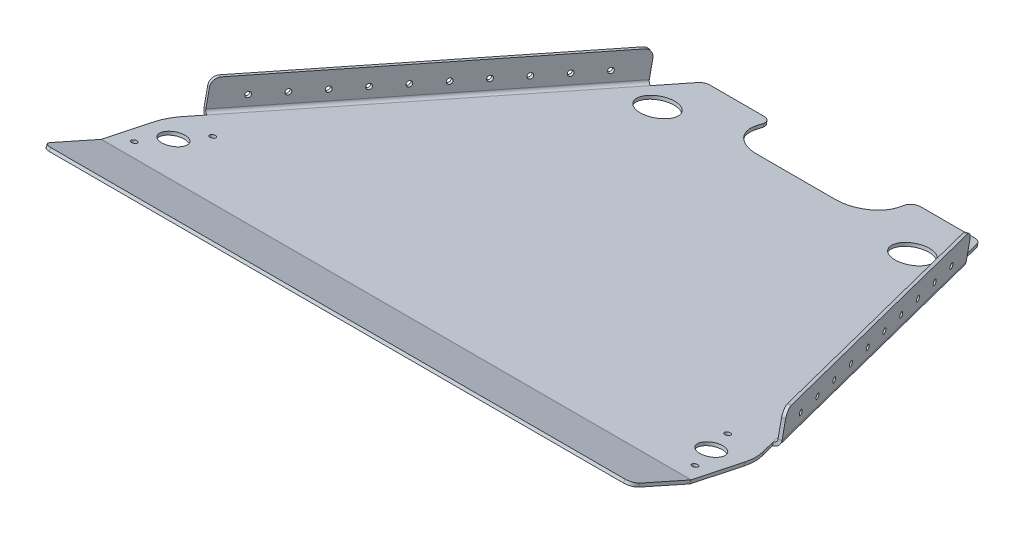
SolidWorks part; units mm, degrees
note: The reader was unsure of these and kept them because the rebuilt part matched: flange length of "Edge-Flange1", "Edge-Flange3".
material "PC High Viscosity"
ref_plane "Front Plane" through (0, 0, 0) normal (0, 0, 1) x (1, 0, 0)
ref_plane "Top Plane" through (0, 0, 0) normal (0, 1, 0) x (1, 0, 0)
ref_plane "Right Plane" through (0, 0, 0) normal (1, 0, 0) x (0, 0, -1)
sketch "Sketch3" plane through (0, 0, 0) normal (1, 0, 0) x (0, 0, -1)
  line L2 (0, 0) -> (233.2096, 0) construction
  line L7 (0, 25.4) -> (233.2096, 25.4) construction
  line L8 (0, 25.4) -> (233.2096, 25.4) construction
  line L9 (18.9735, 25.4) -> (-49981.0265, 25.4) construction
  line L10 (-119.4976, 25.4) -> (-118.9695, 27.8845)
  line L11 (-119.4976, 25.4) -> (-477.9904, 101.6)
  line L12 (-477.7235, 104.14) -> (-118.9695, 27.8845)
  line L16 (-477.7235, 104.14) -> (-477.9904, 101.6)
  circle A0 centre (4.6096, 88.9) radius 88.9 construction
  dimension "D3" = 177.8
  dimension "D4" = 228.6
  dimension "D8" = 25.4
ref_plane "Plane1" through (0, 0, 0) normal (0, 0.9781, -0.2079) x (0, 0.2079, 0.9781)
sketch "Sketch19" plane through (0, 0, 0) normal (0, 0.9781, -0.2079) x (1, 0, 0)
  line L0 (238.125, -441.336) -> (111.125, -127)
  line L1 (-111.125, -127) -> (-57.15, -127)
  line L3 (-238.125, -495.3) -> (238.125, -495.3)
  line L5 (-111.125, -127) -> (-238.125, -441.336)
  line L7 (-238.125, -495.3) -> (-238.125, -441.336)
  line L8 (-238.125, -440.7496) -> (-238.125, -428.0575) construction
  line L9 (238.125, -441.336) -> (238.125, -495.3)
  line L10 (-238.125, -441.336) -> (-259.9279, -495.3) construction
  line L11 (-57.15, -139.7) -> (-57.15, -127)
  line L12 (-31.75, -165.1) -> (31.75, -165.1)
  line L13 (57.15, -139.7) -> (57.15, -127)
  line L14 (57.15, -127) -> (111.125, -127)
  line L15 (238.125, -441.336) -> (259.9279, -495.3) construction
  arc A0 (-57.15, -139.7) -> (-31.75, -165.1) centre (-31.75, -139.7) ccw
  arc A1 (31.75, -165.1) -> (57.15, -139.7) centre (31.75, -139.7) ccw
  point P18 (0, -495.3)
  point P22 (0, -165.1)
  dimension "D5" = 50.8
  dimension "D6" = 114.3
  dimension "D1" = 495.3
  dimension "D2" = 222.25
  dimension "D3" = 68
  dimension "D4" = 127
  dimension "D7" = 38.1
base flange "Base-Flange1" sketch "Sketch19" thickness 2.54 reverse thickness direction no parameters "D1"=2.54
edge flange "Edge-Flange1" sketch "Sketch23" flange profiles "Sketch23", "Sketch25" flange angle 90 flange length 25.4 flange position bend outside bend radius 2.54 thickness 2.54 relief rectangular parameters "D6"=10, "D8"=0.254
bend "EdgeBend5" bend radius 2.54 bend angle 90 parameters "D5"=1
bend "EdgeBend6" bend radius 2.54 bend angle 90 parameters "D5"=2
sketch "Sketch23" plane through (-51.42, -4.3194, -20.321) normal (-0.9272, -0.0779, -0.3664) x (-0.3746, 0.1928, 0.9069)
  line L0 (159.3805, 0) -> (498.4028, 0) construction
  line L1 (193.6028, 0) -> (473.0028, 0)
  line L2 (193.6028, 0) -> (193.6028, 22.86)
  line L3 (193.6028, 22.86) -> (473.0028, 22.86)
  line L4 (473.0028, 22.86) -> (473.0028, 0)
  dimension "D1" = 25.4
  dimension "D2" = 279.4
sketch "Sketch25" plane through (51.42, -4.3194, -20.321) normal (0.9272, -0.0779, -0.3664) x (-0.3746, -0.1928, -0.9069)
  line L0 (-498.4028, 0) -> (-159.3805, 0) construction
  line L1 (-473.0028, 0) -> (-193.6028, 0)
  line L2 (-473.0028, 0) -> (-473.0028, 22.86)
  line L3 (-473.0028, 22.86) -> (-193.6028, 22.86)
  line L4 (-193.6028, 22.86) -> (-193.6028, 0)
  dimension "D1" = 25.4
  dimension "D2" = 279.4
sketch "Sketch12" plane through (0, 0, 0) normal (0, 0.9781, -0.2079) x (1, 0, 0)
  circle A0 centre (-217.1397, -457.2) radius 9.525
  circle A1 centre (-102.8859, -174.412) radius 14.2875
  circle A3 centre (-102.8859, -174.412) radius 14.2875 construction
  circle A4 centre (-217.1397, -457.2) radius 14.325 construction
  dimension "D1" = 19.05
extrude "Cut-Extrude2" cut sketch "Sketch12" against normal through all both and the other way through all normal cut yes
mirror "Mirror8" about plane through (0, 0, 0) normal (1, 0, 0) of "Cut-Extrude2"
edge flange "Edge-Flange3" sketch "Sketch29" flange angle 168 flange length 51.8738 flange position material outside bend radius 2.54 thickness 2.54 relief rectangular parameters "D6"=10
bend "EdgeBend7" bend radius 2.54 bend angle 12 parameters "D5"=3
sketch "Sketch29" plane through (0, 102.9787, 484.4765) normal (0, -0.9135, 0.4067) x (1, 0, 0)
  line L0 (-238.125, 0) -> (238.125, 0) construction
  line L1 (-238.125, 0) -> (238.125, 0)
  line L2 (-238.125, 0) -> (-238.125, 51.6069)
  line L3 (-238.125, 51.6069) -> (238.125, 51.6069)
  line L4 (238.125, 51.6069) -> (238.125, 0)
  line L5 (-228.6, 32.5569) -> (228.6, 32.5569) construction
  dimension "D1" = 19.05
hole_wizard "1/4 (0.25) Diameter Hole1" positions "Sketch32" profile "Sketch33" hole size "1/4" standard "ANSI Inch" end condition up to next
sketch "Sketch32" plane through (56.1301, -4.715, -22.1825) normal (0.9272, -0.0779, -0.3664) x (-0.3652, 0.0296, -0.9304)
  line L0 (-188.1892, 45.534) -> (-183.67, 65.3451) construction
  line L1 (-183.67, 65.3451) -> (-456.0724, 127.4841) construction
  point P0 (-211.2583, 58.6122)
  point P15 (-236.0222, 64.2612)
  point P16 (-260.7861, 69.9102)
  point P17 (-285.5499, 75.5592)
  point P18 (-310.3138, 81.2082)
  point P19 (-335.0776, 86.8572)
  point P20 (-359.8415, 92.5062)
  point P21 (-384.6054, 98.1552)
  point P22 (-409.3692, 103.8042)
  point P23 (-434.1331, 109.4532)
  dimension "D1" = 25.4
  dimension "D2" = 12.7
  dimension "D3" = 10
sketch "Sketch33" plane through (138.17, 47.4406, 174.3238) normal (0.3209, 0.6697, 0.6697) x (-0.1932, 0.7385, -0.6459)
  line L0 (0, 0) -> (0, 356.1849)
  line L1 (0, 356.1849) -> (2.0955, 356.1849)
  line L2 (2.0955, 356.1849) -> (2.0955, 0)
  line L5 (2.0955, 0) -> (0, 0)
  line L11 (0, -6.35) -> (0, 107.95) construction
  dimension "Thru Hole Dia." = 4.191
  dimension "Thru Hole Depth" = 356.1849
mirror "Mirror9" about plane through (0, 0, 0) normal (1, 0, 0) of "1/4 (0.25) Diameter Hole1"
hole_wizard "#8 Clearance Hole1" positions "Sketch34" profile "Sketch36" hole size "#8" standard "ANSI Inch" end condition through all
sketch "Sketch34" plane through (0, -2.4845, 0.5281) normal (0, -0.9781, 0.2079) x (-1, 0, 0)
  circle A1 centre (226.4107, -480.1466) radius 2.1526 construction
  circle A2 centre (207.8687, -434.2534) radius 2.1526 construction
  circle A3 centre (-226.4107, -480.1466) radius 2.1527 construction
  circle A4 centre (-207.8687, -434.2534) radius 2.1526 construction
  point P0 (-226.4107, -480.1466)
  point P4 (-207.8687, -434.2534)
  point P8 (207.8687, -434.2534)
  point P10 (226.4107, -480.1466)
sketch "Sketch36" plane through (226.4107, 97.3436, 470.1823) normal (1, 0, 0) x (0, -0.2079, -0.9781)
  line L0 (0, 0) -> (0, 97.9723)
  line L1 (0, 97.9723) -> (2.2479, 97.9723)
  line L2 (2.2479, 97.9723) -> (2.2479, 0)
  line L5 (2.2479, 0) -> (0, 0)
  line L11 (0, -6.35) -> (0, 107.95) construction
  dimension "Thru Hole Dia." = 4.4958
  dimension "Thru Hole Depth" = 97.9723
fillet "Fillet1" radius 50.8 2 edges at (238.125, 90.5167, 431.9558) (-238.125, 90.5167, 431.9558)
fillet "Fillet2" radius 6.35 10 edges at (232.1426, 108.9262, 402.507) (127.4775, 55.0656, 149.1128) (111.125, 25.1625, 124.4888) (57.15, 25.1625, 124.4888) (-57.15, 25.1625, 124.4888) (-111.125, 25.1625, 124.4888) (-127.4775, 55.0656, 149.1128) (-232.1426, 108.9262, 402.507) (-238.125, 122.8089, 532.1383) (238.125, 122.8089, 532.1383)
sketch "Bend-Lines1" [suppressed] plane through (0, 0, 0) normal (0, 1, 0) x (1, 0, 0)
sketch "Bounding-Box1" [suppressed] plane through (0, 0, 0) normal (0, 1, 0) x (1, 0, 0)
sheet metal parameters "Sheet-Metal6" thickness 2.54 parameters "D1"=2.54
flat pattern "Flat-Pattern10" [suppressed]
sketch "Bend-Lines3" plane through (0, 0, 0) normal (0, -0.9781, 0.2079) x (-1, 0, 0)
  line L0 (-256.788, -487.5821) -> (-113.913, -121.0804) construction
  line L1 (113.913, -121.0804) -> (256.788, -487.5821) construction
  line L2 (-256.788, -487.5821) -> (-113.913, -121.0804) construction
  line L3 (113.913, -121.0804) -> (256.788, -487.5821) construction
sketch3d "Bounding-Box3" [suppressed]
  line L0 (-278.5083, -112.6131, 0) -> (278.5083, -112.6131, 0) construction
  line L1 (-278.5083, -488.669, 0) -> (278.5083, -488.669, 0) construction
  line L2 (-278.5083, -112.6131, 0) -> (-278.5083, -488.669, 0) construction
  line L3 (278.5083, -112.6131, 0) -> (278.5083, -488.669, 0) construction
bend of the flat pattern "Flatten-<EdgeBend5>1"
bend of the flat pattern "Flatten-<EdgeBend6>1"
sheet metal parameters "Sheet-Metal7" thickness 2.54 parameters "D1"=2.54
flat pattern "Flat-Pattern10" [suppressed]
sketch "Bend-Lines3" plane through (0, 2.4845, -0.5281) normal (0, 0.9781, -0.2079) x (1, 0, 0)
  line L0 (279.4, -488.801) -> (-279.4, -488.801) construction
  line L1 (279.4, -488.801) -> (-279.4, -488.801) construction
  line L2 (87.0479, -123.1306) -> (276.9383, -488.1933) construction
  line L3 (87.0479, -123.1306) -> (276.9383, -488.1933) construction
sketch3d "Bounding-Box3" [suppressed]
  line L0 (18.8297, 376.5632, 0) -> (-558.8, 376.5632, 0) construction
  line L1 (18.8297, -25.3971, 0) -> (-558.8, -25.3971, 0) construction
  line L2 (18.8297, 376.5632, 0) -> (18.8297, -25.3971, 0) construction
  line L3 (-558.8, 376.5632, 0) -> (-558.8, -25.3971, 0) construction
bend of the flat pattern "Flatten-<EdgeBend5>3"
bend of the flat pattern "Flatten-<EdgeBend6>3"
sheet metal parameters "Sheet-Metal8" thickness 2.54 parameters "D1"=2.54
flat pattern "Flat-Pattern10" [suppressed]
sketch "Bend-Lines3" plane through (0, 2.4845, -0.5281) normal (0, 0.9781, -0.2079) x (1, 0, 0)
  point P2 (91.5547, -120.7864)
  point P3 (282.0547, -487.0212)
  point P4 (-282.0547, -487.0212)
  point P5 (-91.5547, -120.7864)
sketch3d "Bounding-Box3" [suppressed]
  line L0 (0, 366.7687, 0) -> (-558.8, 366.7687, 0) construction
  line L1 (0, 0, 0) -> (-558.8, 0, 0) construction
  line L2 (0, 366.7687, 0) -> (0, 0, 0) construction
  line L3 (-558.8, 366.7687, 0) -> (-558.8, 0, 0) construction
bend of the flat pattern "Flatten-<EdgeBend5>4"
bend of the flat pattern "Flatten-<EdgeBend6>4"
sheet metal parameters "Sheet-Metal9" thickness 2.54 parameters "D1"=2.54
flat pattern "Flat-Pattern10"
sketch "Bend-Lines3" plane through (0, -2.4845, 0.5281) normal (0, -0.9781, 0.2079) x (-1, 0, 0)
  line L0 (253.948, -489.068) -> (-253.948, -489.068) construction
  line L1 (-247.5685, -464.1822) -> (-113.9133, -121.0811) construction
  line L2 (113.9133, -121.0811) -> (247.5685, -464.1822) construction
  line L3 (253.948, -489.068) -> (-253.948, -489.068) construction
  line L4 (-247.5685, -464.1822) -> (-113.9133, -121.0811) construction
  line L5 (113.9133, -121.0811) -> (247.5685, -464.1822) construction
sketch3d "Bounding-Box3" [suppressed]
  line L0 (-269.2909, -112.6191, 0) -> (269.2909, -112.6191, 0) construction
  line L1 (-269.2909, -553.957, 0) -> (269.2909, -553.957, 0) construction
  line L2 (-269.2909, -112.6191, 0) -> (-269.2909, -553.957, 0) construction
  line L3 (269.2909, -112.6191, 0) -> (269.2909, -553.957, 0) construction
bend of the flat pattern "Flatten-<EdgeBend7>1"
bend of the flat pattern "Flatten-<EdgeBend5>2"
bend of the flat pattern "Flatten-<EdgeBend6>2"
sheet metal parameters "Sheet-Metal10" thickness 2.54 parameters "D1"=2.54
flat pattern "Flat-Pattern10"
sketch "Bend-Lines3" plane through (0, 0, 0) normal (0, 1, 0) x (1, 0, 0)
sketch3d "Bounding-Box3" [suppressed]
  line L0 (254, -122.1673, 0) -> (-254, -122.1673, 0) construction
  line L1 (254, -488.936, 0) -> (-254, -488.936, 0) construction
  line L2 (254, -122.1673, 0) -> (254, -488.936, 0) construction
  line L3 (-254, -122.1673, 0) -> (-254, -488.936, 0) construction
sheet metal parameters "Sheet-Metal11" thickness 2.54 parameters "D1"=2.54
flat pattern "Flat-Pattern10"
sketch "Bend-Lines3" plane through (0, -2.4845, 0.5281) normal (0, -0.9781, 0.2079) x (-1, 0, 0)
  line L0 (253.948, -489.068) -> (-253.948, -489.068) construction
  line L1 (-247.5685, -464.1822) -> (-113.9133, -121.0811) construction
  line L2 (113.9133, -121.0811) -> (247.5685, -464.1822) construction
  line L3 (253.948, -489.068) -> (-253.948, -489.068) construction
  line L4 (-247.5685, -464.1822) -> (-113.9133, -121.0811) construction
  line L5 (113.9133, -121.0811) -> (247.5685, -464.1822) construction
sketch3d "Bounding-Box3" [suppressed]
  line L0 (-269.2909, -112.6191, 0) -> (269.2909, -112.6191, 0) construction
  line L1 (-269.2909, -553.957, 0) -> (269.2909, -553.957, 0) construction
  line L2 (-269.2909, -112.6191, 0) -> (-269.2909, -553.957, 0) construction
  line L3 (269.2909, -112.6191, 0) -> (269.2909, -553.957, 0) construction
bend of the flat pattern "Flatten-<EdgeBend7>1"
bend of the flat pattern "Flatten-<EdgeBend5>2"
bend of the flat pattern "Flatten-<EdgeBend6>2"
sheet metal parameters "Sheet-Metal12" thickness 2.54 parameters "D1"=2.54
flat pattern "Flat-Pattern10"
sketch "Bend-Lines3" plane through (0, -2.4845, 0.5281) normal (0, -0.9781, 0.2079) x (-1, 0, 0)
  line L0 (238.125, -495.432) -> (-238.125, -495.432) construction
  line L1 (-231.3845, -416.6646) -> (-126.7194, -157.6094) construction
  line L2 (126.7194, -157.6094) -> (231.3845, -416.6646) construction
  line L3 (238.125, -495.432) -> (-238.125, -495.432) construction
  line L4 (-231.3845, -416.6646) -> (-126.7194, -157.6094) construction
  line L5 (126.7194, -157.6094) -> (231.3845, -416.6646) construction
sketch3d "Bounding-Box3" [suppressed]
  line L0 (-284.7493, 12.7, 0) -> (221.2493, 12.7, 0) construction
  line L1 (-284.7493, -407.4691, 0) -> (221.2493, -407.4691, 0) construction
  line L2 (-284.7493, 12.7, 0) -> (-284.7493, -407.4691, 0) construction
  line L3 (221.2493, 12.7, 0) -> (221.2493, -407.4691, 0) construction
bend of the flat pattern "Flatten-<EdgeBend7>1"
bend of the flat pattern "Flatten-<EdgeBend5>2"
bend of the flat pattern "Flatten-<EdgeBend6>2"
sheet metal parameters "Sheet-Metal13" thickness 2.54 parameters "D1"=2.54
flat pattern "Flat-Pattern10"
sketch "Bend-Lines3" plane through (0, -2.4845, 0.5281) normal (0, -0.9781, 0.2079) x (-1, 0, 0)
  line L0 (238.125, -495.432) -> (-238.125, -495.432) construction
  line L1 (-231.3845, -416.6646) -> (-126.7194, -157.6094) construction
  line L2 (126.7194, -157.6094) -> (231.3845, -416.6646) construction
  line L3 (238.125, -495.432) -> (-238.125, -495.432) construction
  line L4 (-231.3845, -416.6646) -> (-126.7194, -157.6094) construction
  line L5 (126.7194, -157.6094) -> (231.3845, -416.6646) construction
sketch3d "Bounding-Box3" [suppressed]
  line L0 (-282.8328, 12.7, 0) -> (219.3328, 12.7, 0) construction
  line L1 (-282.8328, -407.4709, 0) -> (219.3328, -407.4709, 0) construction
  line L2 (-282.8328, 12.7, 0) -> (-282.8328, -407.4709, 0) construction
  line L3 (219.3328, 12.7, 0) -> (219.3328, -407.4709, 0) construction
bend of the flat pattern "Flatten-<EdgeBend7>1"
bend of the flat pattern "Flatten-<EdgeBend5>2"
bend of the flat pattern "Flatten-<EdgeBend6>2"
